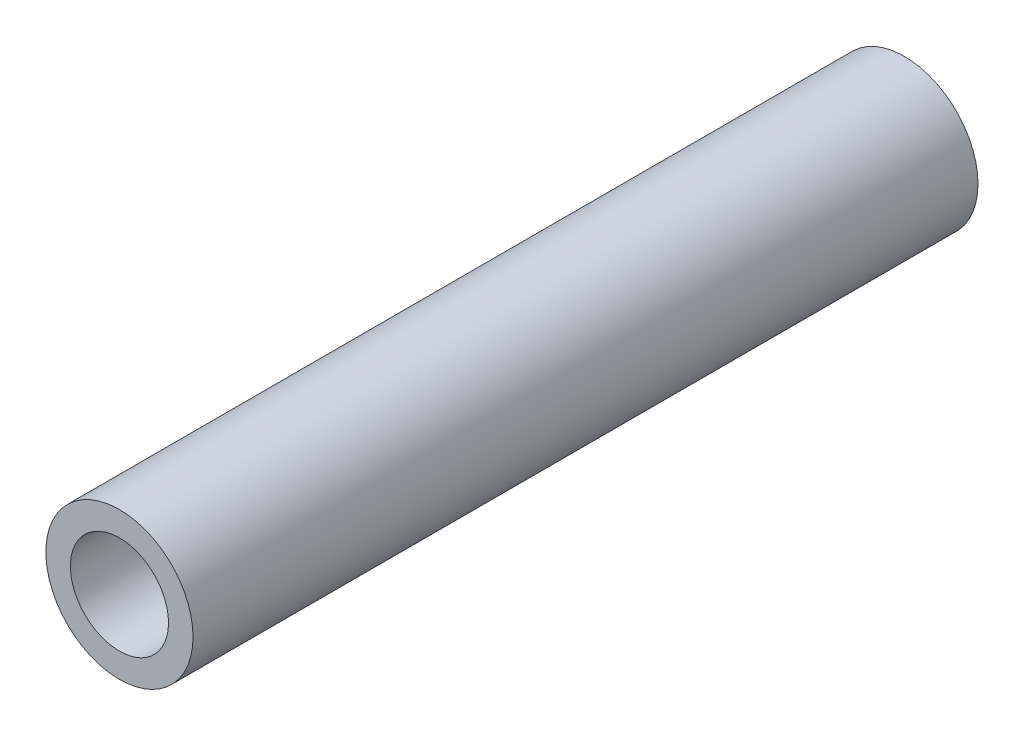
SolidWorks part; units mm, degrees
ref_plane "Front" through (0, 0, 0) normal (0, 0, 1) x (1, 0, 0)
ref_plane "Top" through (0, 0, 0) normal (0, 1, 0) x (1, 0, 0)
ref_plane "Right" through (0, 0, 0) normal (1, 0, 0) x (0, 0, -1)
sketch "Esquisse1" plane through (0, 0, 0) normal (0, 0, 1) x (1, 0, 0)
  circle A0 centre (0, 0) radius 2
  circle A1 centre (0, 0) radius 3
  dimension "D1" = 6
  dimension "D2" = 4
extrude "Boss.-Extru.1" add sketch "Esquisse1" along normal blind 32
